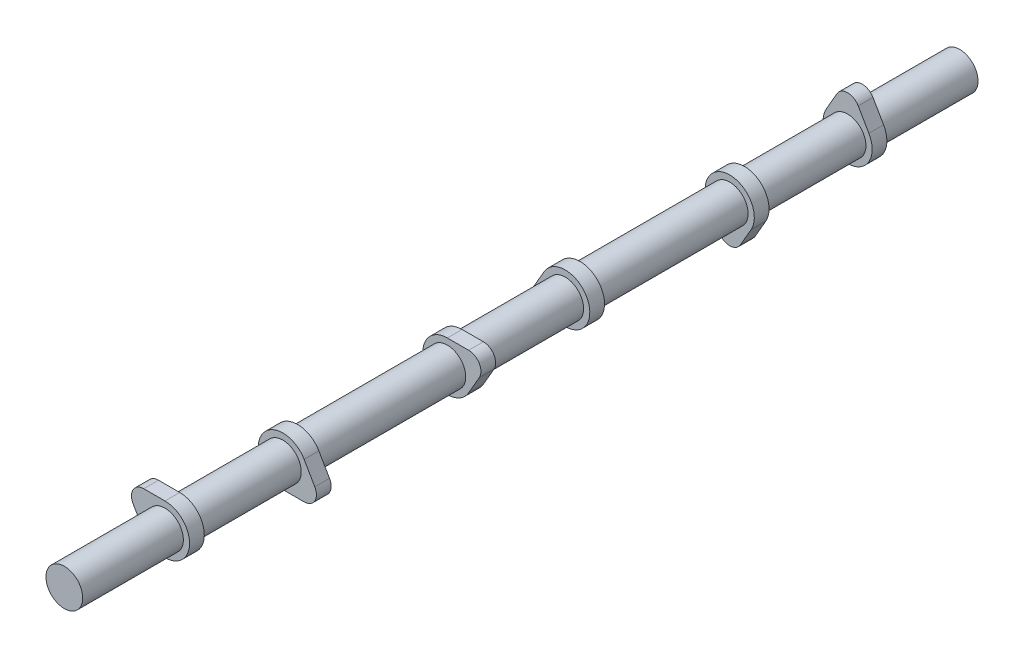
SolidWorks part; units mm, degrees
material "Plain Carbon Steel"
ref_plane "Front Plane" through (0, 0, 0) normal (0, 0, 1) x (1, 0, 0)
ref_plane "Top Plane" through (0, 0, 0) normal (0, 1, 0) x (1, 0, 0)
ref_plane "Right Plane" through (0, 0, 0) normal (1, 0, 0) x (0, 0, -1)
sketch "Sketch1" plane through (0, 0, 0) normal (0, 0, 1) x (1, 0, 0)
  line L0 (0, 40.1879) -> (0, -38.9442) construction
  line L1 (-62.8082, 0) -> (75.2455, 0) construction
  line L2 (-5.4993, 15.875) -> (-10.9985, 6.35)
  line L3 (5.4993, 15.875) -> (10.9985, 6.35)
  arc A0 (-10.9985, 6.35) -> (10.9985, 6.35) centre (0, 0) ccw
  arc A2 (5.4993, 15.875) -> (-5.4993, 15.875) centre (0, 12.7) ccw
  dimension "D1" = 25.4
  dimension "D3" = 12.7
extrude "Boss-Extrude1" add sketch "Sketch1" along normal blind 7.62
ref_axis "Axis1" through (0, 0, 282.6583) along (0, 0, -1)
move or copy body "Body-Move/Copy1" bodies to move or copy 101 copy yes number of copies 1 translate (0, 0, 60.96) parameters "D1"=0, "D2"=0, "D3"=0
move or copy body "Body-Move/Copy3" bodies to move or copy 102 copy no rotation origin (0, 0, 0) rotation axis (0, 0, 1) rotation angle 180
sketch "Sketch2" plane through (0, 0, 0) normal (0, 0, 1) x (1, 0, 0)
  circle A0 centre (0, 0) radius 9.5
  dimension "D1" = 19
extrude "Boss-Extrude2" add sketch "Sketch2" along normal blind 146.05 from offset 25.4 offset against normal yes
pattern_linear "LPattern1" count 3 spacing 146.05 along (0, 0, 1) of bodies 105
move or copy body "Body-Move/Copy4" bodies to move or copy 106 copy no rotation origin (0, 0, 0) rotation axis (0, 0, 1) rotation angle 120
move or copy body "Body-Move/Copy5" bodies to move or copy 107 copy no rotation origin (0, 0, 0) rotation axis (0, 0, -1) rotation angle 120
sketch "Sketch4" plane through (0, 0, -25.4) normal (0, 0, -1) x (-1, 0, 0)
  circle A0 centre (0, 0) radius 9.5 construction
  circle A1 centre (0, 0) radius 9.5
extrude "Boss-Extrude3" add sketch "Sketch4" along normal blind 24.94
combine bodies "Combine1" operation type add bodies to combine 109 108 110
